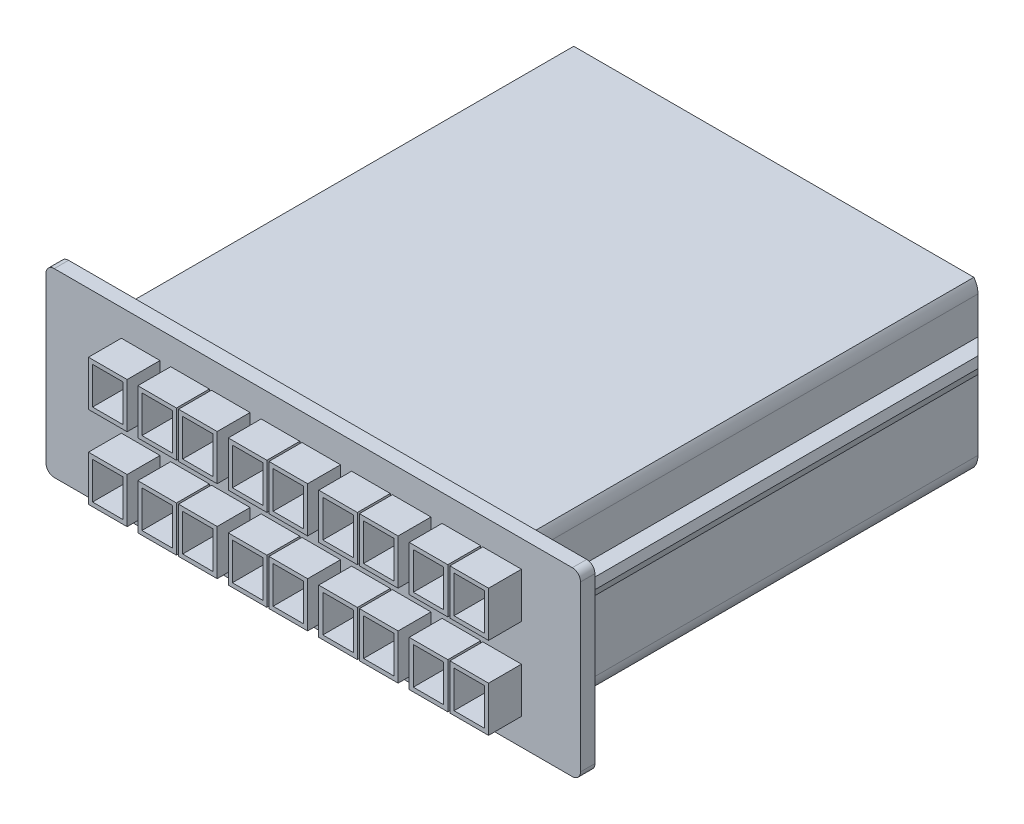
SolidWorks part; units mm, degrees
ref_plane "前视基准面" through (0, 0, 0) normal (0, 0, 1) x (1, 0, 0)
ref_plane "上视基准面" through (0, 0, 0) normal (0, 1, 0) x (1, 0, 0)
ref_plane "右视基准面" through (0, 0, 0) normal (1, 0, 0) x (0, 0, -1)
sketch "草图1" plane through (0, 0, 0) normal (0, 1, 0) x (1, 0, 0)
  line L0 (0, 117.5385) -> (0, -101.5385) construction
  line L1 (-65, 56) -> (65, 56)
  line L2 (-65, 56) -> (-65, -56)
  line L3 (-65, -56) -> (65, -56)
  line L4 (65, 56) -> (65, -56)
  line L5 (-199.7949, 0) -> (126.7692, 0) construction
  dimension "D1" = 112
  dimension "D2" = 130
extrude "凸台-拉伸1" add sketch "草图1" along normal blind 22 and the other way blind 22
sketch "草图2" plane through (0, 22, 0) normal (0, 1, 0) x (1, 0, 0)
  line L0 (0, 65.407) -> (0, -78.0498) construction
  line L1 (54.6587, 56) -> (54.6587, -52.5062)
  line L2 (-65, 56) -> (-54.6587, 56)
  line L3 (-65, 56) -> (-65, -52.5062)
  line L4 (-65, -52.5062) -> (-54.6587, -52.5062)
  line L5 (-54.6587, 56) -> (-54.6587, -52.5062)
  line L6 (65, -52.5062) -> (54.6587, -52.5062)
  line L7 (65, 56) -> (65, -52.5062)
  line L8 (65, 56) -> (54.6587, 56)
extrude "切除-拉伸1" cut sketch "草图2" against normal through all
sketch "草图3" plane through (-54.6587, 0, 0) normal (-1, 0, 0) x (0, 0, 1)
  line L0 (52.5062, -22) -> (52.5062, 22) construction
  line L1 (-56, 22) -> (52.5062, 22)
  line L2 (-56, 22) -> (-56, 7.9602)
  line L3 (-56, 7.9602) -> (52.5062, 7.9602)
  line L4 (52.5062, 22) -> (52.5062, 7.9602)
  line L6 (-56, -22) -> (52.5062, -22)
  line L7 (-56, -22) -> (-56, 4.0329)
  line L8 (-56, 4.0329) -> (52.5062, 4.0329)
  line L9 (52.5062, -22) -> (52.5062, 4.0329)
extrude "切除-拉伸2" cut sketch "草图3" against normal blind 5
mirror "镜向1" about plane through (0, 0, 0) normal (1, 0, 0) of "切除-拉伸2"
chamfer "倒角1" distance 5 angle 45 2 edges at (-54.6587, 5.9966, -56) (54.6587, 5.9966, -56)
fillet "圆角1" radius 5 4 edges at (49.6587, 22, -1.7469) (49.6587, -22, -1.7469) (-49.6587, -22, -1.7469) (-49.6587, 22, -1.7469)
chamfer "倒角2" distance 1 angle 70 4 edges at (54.6587, 7.9602, 0.7531) (54.6587, 4.0329, 0.7531) (-54.6587, 4.0329, 0.7531) (-54.6587, 7.9602, 0.7531) first distance on face at (52.1587, 7.9602, -0.4969) first distance on face at (52.1587, 4.0329, -0.4969) first distance on face at (-54.6587, 5.9966, 0.7531)
fillet "圆角2" radius 2 4 edges at (65, 22, 54.2531) (65, -22, 54.2531) (-65, -22, 54.2531) (-65, 22, 54.2531)
sketch "草图4" plane through (0, 0, 56) normal (0, 0, 1) x (1, 0, 0)
  line L0 (-76.0186, -10) -> (82.5881, -10) construction
  line L1 (-34.6736, -4.5) -> (-25.2736, -4.5)
  line L2 (-46.6736, -4.5) -> (-37.2736, -4.5)
  line L3 (-46.6736, -4.5) -> (-46.6736, -15.5)
  line L4 (-46.6736, -15.5) -> (-37.2736, -15.5)
  line L5 (-37.2736, -4.5) -> (-37.2736, -15.5)
  line L6 (-34.6736, -4.5) -> (-34.6736, -15.5)
  line L7 (-34.6736, -15.5) -> (-25.2736, -15.5)
  line L8 (-25.2736, -4.5) -> (-25.2736, -15.5)
  line L9 (-24.7736, -4.5) -> (-15.3736, -4.5)
  line L10 (-24.7736, -4.5) -> (-24.7736, -15.5)
  line L11 (-24.7736, -15.5) -> (-15.3736, -15.5)
  line L12 (-15.3736, -4.5) -> (-15.3736, -15.5)
  line L13 (-12.6736, -4.5) -> (-3.2736, -4.5)
  line L14 (-12.6736, -4.5) -> (-12.6736, -15.5)
  line L15 (-12.6736, -15.5) -> (-3.2736, -15.5)
  line L16 (-3.2736, -4.5) -> (-3.2736, -15.5)
  line L17 (-2.7736, -4.5) -> (6.6264, -4.5)
  line L18 (-2.7736, -4.5) -> (-2.7736, -15.5)
  line L19 (-2.7736, -15.5) -> (6.6264, -15.5)
  line L20 (6.6264, -4.5) -> (6.6264, -15.5)
  line L21 (9.3264, -4.5) -> (18.7264, -4.5)
  line L22 (9.3264, -4.5) -> (9.3264, -15.5)
  line L23 (9.3264, -15.5) -> (18.7264, -15.5)
  line L24 (18.7264, -4.5) -> (18.7264, -15.5)
  line L25 (19.2264, -4.5) -> (28.6264, -4.5)
  line L26 (19.2264, -4.5) -> (19.2264, -15.5)
  line L27 (19.2264, -15.5) -> (28.6264, -15.5)
  line L28 (28.6264, -4.5) -> (28.6264, -15.5)
  line L29 (31.3264, -4.5) -> (40.7264, -4.5)
  line L30 (31.3264, -4.5) -> (31.3264, -15.5)
  line L31 (31.3264, -15.5) -> (40.7264, -15.5)
  line L32 (40.7264, -4.5) -> (40.7264, -15.5)
  line L33 (41.2264, -4.5) -> (50.6264, -4.5)
  line L34 (41.2264, -4.5) -> (41.2264, -15.5)
  line L35 (41.2264, -15.5) -> (50.6264, -15.5)
  line L36 (50.6264, -4.5) -> (50.6264, -15.5)
  line L37 (-33.6736, -5.5) -> (-26.2736, -5.5)
  line L38 (-26.2736, -5.5) -> (-26.2736, -14.5)
  line L39 (-33.6736, -14.5) -> (-26.2736, -14.5)
  line L40 (-33.6736, -5.5) -> (-33.6736, -14.5)
  line L41 (-45.6736, -5.5) -> (-38.2736, -5.5)
  line L42 (-38.2736, -5.5) -> (-38.2736, -14.5)
  line L43 (-45.6736, -14.5) -> (-38.2736, -14.5)
  line L44 (-45.6736, -5.5) -> (-45.6736, -14.5)
  line L45 (-23.7736, -5.5) -> (-16.3736, -5.5)
  line L46 (-16.3736, -5.5) -> (-16.3736, -14.5)
  line L47 (-23.7736, -14.5) -> (-16.3736, -14.5)
  line L48 (-23.7736, -5.5) -> (-23.7736, -14.5)
  line L49 (-11.6736, -5.5) -> (-4.2736, -5.5)
  line L50 (-4.2736, -5.5) -> (-4.2736, -14.5)
  line L51 (-11.6736, -14.5) -> (-4.2736, -14.5)
  line L52 (-11.6736, -5.5) -> (-11.6736, -14.5)
  line L53 (-1.7736, -5.5) -> (5.6264, -5.5)
  line L54 (5.6264, -5.5) -> (5.6264, -14.5)
  line L55 (-1.7736, -14.5) -> (5.6264, -14.5)
  line L56 (-1.7736, -5.5) -> (-1.7736, -14.5)
  line L57 (10.3264, -5.5) -> (17.7264, -5.5)
  line L58 (17.7264, -5.5) -> (17.7264, -14.5)
  line L59 (10.3264, -14.5) -> (17.7264, -14.5)
  line L60 (10.3264, -5.5) -> (10.3264, -14.5)
  line L61 (20.2264, -5.5) -> (27.6264, -5.5)
  line L62 (27.6264, -5.5) -> (27.6264, -14.5)
  line L63 (20.2264, -14.5) -> (27.6264, -14.5)
  line L64 (20.2264, -5.5) -> (20.2264, -14.5)
  line L65 (32.3264, -5.5) -> (39.7264, -5.5)
  line L66 (39.7264, -5.5) -> (39.7264, -14.5)
  line L67 (32.3264, -14.5) -> (39.7264, -14.5)
  line L68 (32.3264, -5.5) -> (32.3264, -14.5)
  line L69 (42.2264, -5.5) -> (49.6264, -5.5)
  line L70 (49.6264, -5.5) -> (49.6264, -14.5)
  line L71 (42.2264, -14.5) -> (49.6264, -14.5)
  line L72 (42.2264, -5.5) -> (42.2264, -14.5)
  line L73 (-78.5208, 0) -> (87.0576, 0) construction
  line L74 (42.2264, 5.5) -> (42.2264, 14.5)
  line L75 (42.2264, 14.5) -> (49.6264, 14.5)
  line L76 (49.6264, 5.5) -> (49.6264, 14.5)
  line L77 (42.2264, 5.5) -> (49.6264, 5.5)
  line L78 (32.3264, 5.5) -> (32.3264, 14.5)
  line L79 (32.3264, 14.5) -> (39.7264, 14.5)
  line L80 (39.7264, 5.5) -> (39.7264, 14.5)
  line L81 (32.3264, 5.5) -> (39.7264, 5.5)
  line L82 (20.2264, 5.5) -> (20.2264, 14.5)
  line L83 (20.2264, 14.5) -> (27.6264, 14.5)
  line L84 (27.6264, 5.5) -> (27.6264, 14.5)
  line L85 (20.2264, 5.5) -> (27.6264, 5.5)
  line L86 (10.3264, 5.5) -> (10.3264, 14.5)
  line L87 (10.3264, 14.5) -> (17.7264, 14.5)
  line L88 (17.7264, 5.5) -> (17.7264, 14.5)
  line L89 (10.3264, 5.5) -> (17.7264, 5.5)
  line L90 (-1.7736, 5.5) -> (-1.7736, 14.5)
  line L91 (-1.7736, 14.5) -> (5.6264, 14.5)
  line L92 (5.6264, 5.5) -> (5.6264, 14.5)
  line L93 (-1.7736, 5.5) -> (5.6264, 5.5)
  line L94 (-11.6736, 5.5) -> (-11.6736, 14.5)
  line L95 (-11.6736, 14.5) -> (-4.2736, 14.5)
  line L96 (-4.2736, 5.5) -> (-4.2736, 14.5)
  line L97 (-11.6736, 5.5) -> (-4.2736, 5.5)
  line L98 (-23.7736, 5.5) -> (-23.7736, 14.5)
  line L99 (-23.7736, 14.5) -> (-16.3736, 14.5)
  line L100 (-16.3736, 5.5) -> (-16.3736, 14.5)
  line L101 (-23.7736, 5.5) -> (-16.3736, 5.5)
  line L102 (-45.6736, 5.5) -> (-45.6736, 14.5)
  line L103 (-45.6736, 14.5) -> (-38.2736, 14.5)
  line L104 (-38.2736, 5.5) -> (-38.2736, 14.5)
  line L105 (-45.6736, 5.5) -> (-38.2736, 5.5)
  line L106 (-33.6736, 5.5) -> (-33.6736, 14.5)
  line L107 (-33.6736, 14.5) -> (-26.2736, 14.5)
  line L108 (-26.2736, 5.5) -> (-26.2736, 14.5)
  line L109 (-33.6736, 5.5) -> (-26.2736, 5.5)
  line L110 (50.6264, 4.5) -> (50.6264, 15.5)
  line L111 (41.2264, 15.5) -> (50.6264, 15.5)
  line L112 (41.2264, 4.5) -> (41.2264, 15.5)
  line L113 (41.2264, 4.5) -> (50.6264, 4.5)
  line L114 (40.7264, 4.5) -> (40.7264, 15.5)
  line L115 (31.3264, 15.5) -> (40.7264, 15.5)
  line L116 (31.3264, 4.5) -> (31.3264, 15.5)
  line L117 (31.3264, 4.5) -> (40.7264, 4.5)
  line L118 (28.6264, 4.5) -> (28.6264, 15.5)
  line L119 (19.2264, 15.5) -> (28.6264, 15.5)
  line L120 (19.2264, 4.5) -> (19.2264, 15.5)
  line L121 (19.2264, 4.5) -> (28.6264, 4.5)
  line L122 (18.7264, 4.5) -> (18.7264, 15.5)
  line L123 (9.3264, 15.5) -> (18.7264, 15.5)
  line L124 (9.3264, 4.5) -> (9.3264, 15.5)
  line L125 (9.3264, 4.5) -> (18.7264, 4.5)
  line L126 (6.6264, 4.5) -> (6.6264, 15.5)
  line L127 (-2.7736, 15.5) -> (6.6264, 15.5)
  line L128 (-2.7736, 4.5) -> (-2.7736, 15.5)
  line L129 (-2.7736, 4.5) -> (6.6264, 4.5)
  line L130 (-3.2736, 4.5) -> (-3.2736, 15.5)
  line L131 (-12.6736, 15.5) -> (-3.2736, 15.5)
  line L132 (-12.6736, 4.5) -> (-12.6736, 15.5)
  line L133 (-12.6736, 4.5) -> (-3.2736, 4.5)
  line L134 (-15.3736, 4.5) -> (-15.3736, 15.5)
  line L135 (-24.7736, 15.5) -> (-15.3736, 15.5)
  line L136 (-24.7736, 4.5) -> (-24.7736, 15.5)
  line L137 (-24.7736, 4.5) -> (-15.3736, 4.5)
  line L138 (-25.2736, 4.5) -> (-25.2736, 15.5)
  line L139 (-34.6736, 15.5) -> (-25.2736, 15.5)
  line L140 (-34.6736, 4.5) -> (-34.6736, 15.5)
  line L141 (-37.2736, 4.5) -> (-37.2736, 15.5)
  line L142 (-46.6736, 15.5) -> (-37.2736, 15.5)
  line L143 (-46.6736, 4.5) -> (-46.6736, 15.5)
  line L144 (-46.6736, 4.5) -> (-37.2736, 4.5)
  line L145 (-34.6736, 4.5) -> (-25.2736, 4.5)
  dimension "D1" = 9.4
  dimension "D2" = 11
  dimension "D7" = 10
  dimension "D6" = 1
  dimension "D3" = 2
  dimension "D4" = 2
  dimension "D5" = 4
extrude "凸台-拉伸2" add sketch "草图4" along normal blind 8
sketch "草图5" plane through (0, 22, 0) normal (0, 1, 0) x (1, 0, 0)
  line L1 (63, -52.5062) -> (-59.8054, -52.5062)
  line L2 (63, -52.5062) -> (63, 59.2527)
  line L3 (63, 59.2527) -> (-59.8054, 59.2527)
  line L4 (-59.8054, -52.5062) -> (-59.8054, 59.2527)
extrude "切除-拉伸3" cut sketch "草图5" against normal blind 2
mirror "镜向2" about plane through (0, 0, 0) normal (0, 1, 0) of "切除-拉伸3"
